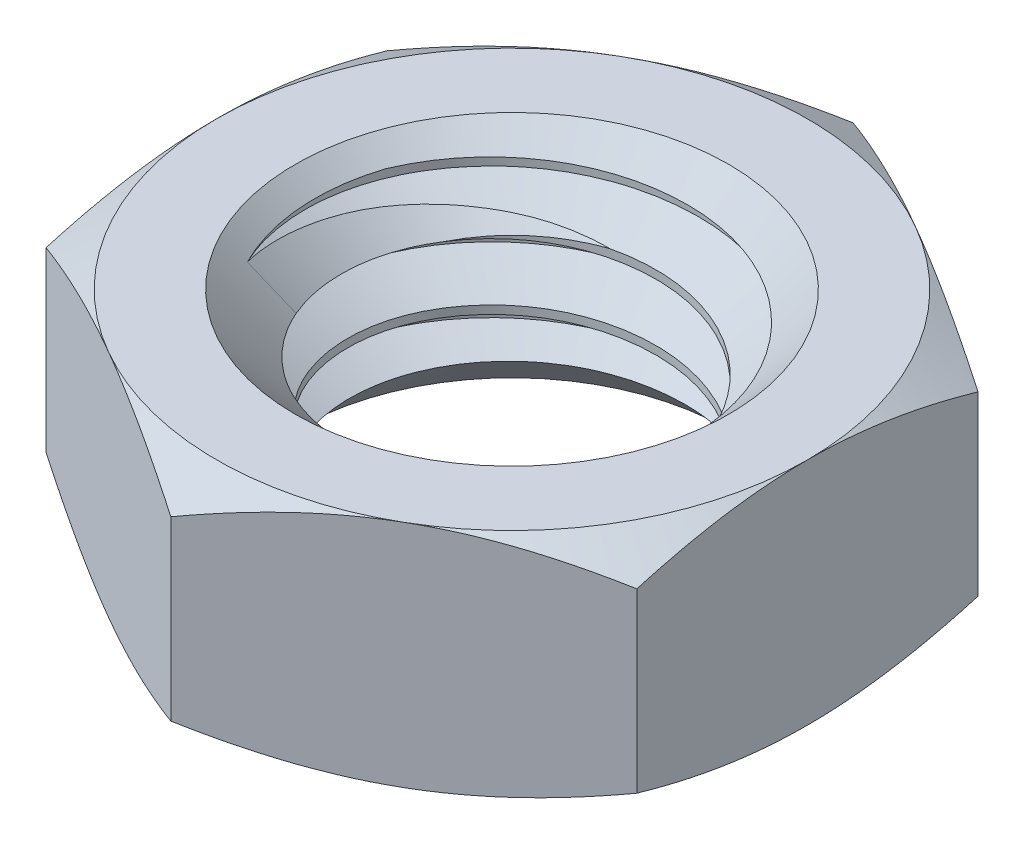
SolidWorks part; units mm, degrees
ref_plane "Front Plane" through (0, 0, 0) normal (0, 0, 1) x (1, 0, 0)
ref_plane "Top Plane" through (0, 0, 0) normal (0, 1, 0) x (1, 0, 0)
ref_plane "Right Plane" through (0, 0, 0) normal (1, 0, 0) x (0, 0, -1)
sketch "Sketch1" plane through (0, 0, 0) normal (0, 0, 1) x (1, 0, 0)
  line L0 (0, -2.7781) -> (0, 2.7781) construction
  line L1 (4.7625, 2.7781) -> (-4.7625, 2.7781) construction
  line L2 (-7.1437, -2.7781) -> (7.1437, -2.7781) construction
  line L3 (4.7625, 2.7781) -> (4.7625, 1.1906) construction
  point P4 (0, 0)
  point P8 (0, 2.7781)
  point P10 (0, -2.7781)
  dimension "Height" = 5.5562
  dimension "Width" = 14.2875
  dimension "Thread Dia" = 9.525
  dimension "Pitch" = 1.5875
sketch "Sketch2" plane through (0, 0, 0) normal (0, 1, 0) x (1, 0, 0)
  line L1 (0, 8.2489) -> (-7.1437, 4.1244)
  line L2 (-7.1437, 4.1244) -> (-7.1437, -4.1244)
  line L3 (-7.1437, -4.1244) -> (0, -8.2489)
  line L4 (0, -8.2489) -> (7.1438, -4.1244)
  line L5 (7.1438, -4.1244) -> (7.1438, 4.1244)
  line L6 (7.1438, 4.1244) -> (0, 8.2489)
  circle A0 centre (0, 0) radius 7.1438 construction
  circle A1 centre (0, 0) radius 4.7625
  point P11 (0, -4.7625)
  point P14 (0, 0)
extrude "Boss-Extrude1" add sketch "Sketch2" along normal up to vertex (2.7781 mm away) and the other way up to vertex (2.7781 mm away) up to point (0, 2.7781, 0) other way up to point (0, -2.7781, 0)
sketch "Sketch3" plane through (0, 0, 0) normal (1, 0, 0) x (0, 0, -1)
  line L0 (-8.2489, 2.1401) -> (-7.1438, 2.7781)
  line L1 (-8.2489, 2.7781) -> (-8.2489, -2.7781) construction
  line L2 (-8.2489, 2.7781) -> (-4.1244, 2.7781) construction
  line L3 (-8.2489, -2.1401) -> (-7.1437, -2.7781)
  line L4 (-8.2489, -2.7781) -> (-4.1244, -2.7781) construction
  line L5 (-8.2489, 2.1401) -> (-8.2489, 2.7781)
  line L6 (-8.2489, 2.7781) -> (-7.1438, 2.7781)
  line L7 (-8.2489, -2.1401) -> (-8.2489, -2.7781)
  line L8 (-8.2489, -2.7781) -> (-7.1437, -2.7781)
  line L9 (-7.1438, 2.7781) -> (-7.1437, -2.7781) construction
  line L10 (-5.2387, 2.7781) -> (-4.7625, 2.7781)
  line L11 (-4.1244, 2.7781) -> (4.1244, 2.7781) construction
  line L12 (-4.7625, 2.7781) -> (-4.7625, 2.3019)
  line L13 (-4.7625, 2.3019) -> (-5.2387, 2.7781)
  line L14 (-5.2387, -2.7781) -> (-4.7625, -2.7781)
  line L15 (-4.1244, -2.7781) -> (4.1244, -2.7781) construction
  line L16 (-4.7625, -2.7781) -> (-4.7625, -2.3019)
  line L17 (-5.2387, -2.7781) -> (-4.7625, -2.3019)
  line L18 (-4.7625, 2.3019) -> (-4.7625, -2.3019) construction
  line L19 (4.7625, 0) -> (-4.7625, 0) construction
  line L22 (0, 2.7781) -> (0, -2.7781) construction
  point P15 (-7.1438, 0)
  point P24 (-4.7625, 0)
  dimension "D1" = 30
  dimension "D2" = 5.2387
revolve "Cut-Revolve1" cut sketch "Sketch3" angle 360 about L22
sketch "Sketch4" plane through (0, 2.7781, 0) normal (0, 1, 0) x (1, 0, 0)
  circle A0 centre (0, 0) radius 4.7625 construction
  circle A1 centre (0, 0) radius 4.7625
extrude "Boss-Extrude2" add sketch "Sketch4" against normal up to surface (5.5563 mm away) separate body up to face at (0, -2.7781, 5.2387)
sketch "Sketch5" plane through (0, 2.7781, 0) normal (0, 1, 0) x (1, 0, 0)
  circle A0 centre (0, 0) radius 4.7625 construction
  circle A1 centre (0, 0) radius 4.7625
curve "Helix/Spiral1" pitch 1.5875 height 7.1437 radius 4.7625 centre (0, 2.7781, 0) axis (0, -1, 0) start towards (0, 0, 1)
sketch "Sketch6" plane through (0, 0, 0) normal (1, 0, 0) x (0, 0, -1)
  line L0 (-4.9344, 2.6789) -> (-3.5595, 3.4727) construction
  line L1 (-3.5595, 3.4727) -> (-4.9344, 4.2664) construction
  line L2 (-4.9344, 4.2664) -> (-4.9344, 2.6789) construction
  line L3 (-3.7314, 3.5719) -> (-3.7314, 3.3734) construction
  line L4 (-4.7625, 4.1672) -> (-4.7625, 2.7781) construction
  line L5 (-4.9344, 3.4727) -> (-4.7625, 3.4727) construction
  line L6 (-3.7314, 3.4727) -> (-3.5595, 3.4727) construction
  line L7 (-4.8484, 3.4727) -> (-4.8484, 2.7285) construction
  line L8 (-4.8484, 2.7285) -> (-4.8484, 4.2168)
  line L9 (-4.8484, 4.2168) -> (-3.7314, 3.5719)
  line L10 (-3.7314, 3.5719) -> (-3.7314, 3.3734)
  line L11 (-3.7314, 3.3734) -> (-4.8484, 2.7285)
  dimension "D1" = 1.5875
  dimension "D2" = 0.1984
sweep "Cut-Sweep1" cut profiles "Sketch6" path "Helix/Spiral1" align with end faces yes
sketch "Sketch7" plane through (0, 0, 0) normal (1, 0, 0) x (0, 0, -1)
  line L0 (-5.2387, 2.7781) -> (-2.8575, 0.3969)
  line L2 (-5.2387, 2.7781) -> (0, 2.7781)
  line L3 (-5.2387, 2.7781) -> (-4.7625, 2.7781) construction
  line L4 (-5.2387, -2.7781) -> (0, -2.7781)
  line L5 (-5.2387, -2.7781) -> (-4.7625, -2.7781) construction
  line L6 (-5.2387, -2.7781) -> (-2.8575, -0.3969)
  line L7 (-5.2387, -2.7781) -> (-4.7625, -2.3019) construction
  line L8 (0, -2.7781) -> (0, 2.7781) construction
  line L9 (0, -2.7781) -> (0, 2.7781) construction
  line L12 (-2.8575, 0.3969) -> (0, 0.3969)
  line L13 (0, 0.3969) -> (0, 2.7781)
  line L14 (-4.7625, 2.3019) -> (-5.2387, 2.7781) construction
  line L15 (-2.8575, -0.3969) -> (0, -0.3969)
  line L16 (0, -0.3969) -> (0, -2.7781)
  dimension "D1" = 2.8575
revolve "Revolve1" add sketch "Sketch7" angle 360 about L9
sketch "Sketch8" plane through (0, 2.7781, 0) normal (0, 1, 0) x (1, 0, 0)
  circle A0 centre (0, 0) radius 5.2387 construction
  circle A1 centre (0, 0) radius 5.2387
extrude "Boss-Extrude3" add sketch "Sketch8" against normal up to surface (5.5563 mm away) up to face at (0, -2.7781, 5.2387)
combine bodies "Combine1" operation type subtract main body 109 bodies to subtract 108
equation "\"D2@Sketch3\"=\"Thread Dia@Sketch1\"*.55"
equation "\"D4@Helix/Spiral1\"=\"Pitch@Sketch1\""
equation "\"D3@Helix/Spiral1\"=\"Height@Sketch1\"+\"Pitch@Sketch1\""
equation "\"D1@Sketch6\"=\"Pitch@Sketch1\""
equation "\"D2@Sketch6\"=\"Pitch@Sketch1\"/8"
equation "\"D1@Sketch7\"=\"Thread Dia@Sketch1\"*.3"
